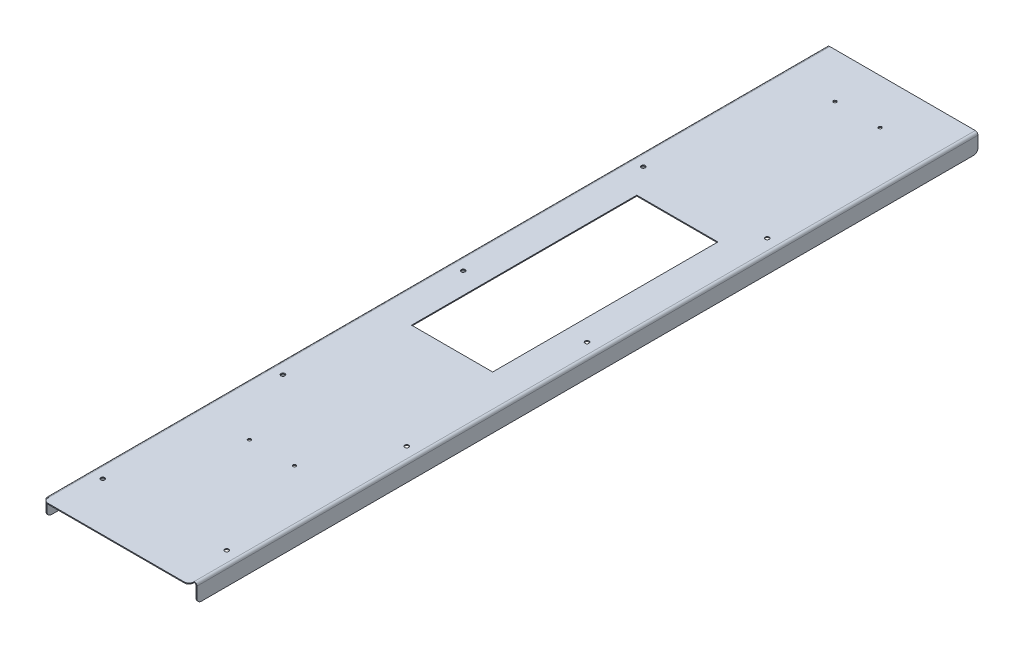
SolidWorks part; units mm, degrees
note: The reader was unsure of these and kept them because the rebuilt part matched: thickness of "Базовая кромка1", "Ребро-кромка1", "Листовой металл3", "Листовой металл4"; flange length of "Ребро-кромка1".
material "AISI 304"
ref_plane "Спереди" through (0, 0, 0) normal (0, 0, 1) x (1, 0, 0)
ref_plane "Сверху" through (0, 0, 0) normal (0, 1, 0) x (1, 0, 0)
ref_plane "Справа" through (0, 0, 0) normal (1, 0, 0) x (0, 0, -1)
sketch "Эскиз1" plane through (0, 0, 0) normal (0, 1, 0) x (1, 0, 0)
  line L0 (0, 373) -> (0, -127) construction
  line L1 (-161.5, 873) -> (161.5, 873)
  line L2 (-161.5, 873) -> (-161.5, -873)
  line L3 (-161.5, -873) -> (161.5, -873)
  line L4 (161.5, 873) -> (161.5, -873)
  line L5 (-161.5, 873) -> (161.5, -873) construction
  line L6 (-161.5, -873) -> (161.5, 873) construction
  line L9 (-90, 373) -> (90, 373)
  line L10 (-90, 373) -> (-90, -127)
  line L12 (-90, -127) -> (90, -127)
  line L13 (90, 373) -> (90, -127)
  line L14 (137.5, 873) -> (137.5, -873) construction
  line L15 (-137.5, 0) -> (137.5, 0) construction
  line L16 (-137.5, -873) -> (-137.5, 873) construction
  line L17 (-50, -527) -> (50, -527) construction
  line L18 (0, 0) -> (0, -527) construction
  line L19 (0, 0) -> (0, 773) construction
  line L20 (-50, 773) -> (50, 773) construction
  circle A0 centre (-137.5, -765) radius 4.5
  circle A1 centre (137.5, -765) radius 4.5
  circle A2 centre (-137.5, -365) radius 4.5
  circle A3 centre (137.5, -365) radius 4.5
  circle A4 centre (-137.5, 35) radius 4.5
  circle A5 centre (137.5, 35) radius 4.5
  circle A6 centre (-137.5, 435) radius 4.5
  circle A7 centre (137.5, 435) radius 4.5
  circle A18 centre (-50, -527) radius 3.5
  circle A19 centre (50, -527) radius 3.5
  circle A20 centre (-50, 773) radius 3.5
  circle A21 centre (50, 773) radius 3.5
  dimension "D6" = 275
  dimension "D7" = 9
  dimension "D8" = 108
  dimension "D11" = 7
  dimension "D1" = 746
  dimension "D2" = 323
  dimension "D3" = 180
  dimension "D4" = 500
  dimension "D5" = 500
  dimension "D10" = 400
  dimension "D12" = 100
  dimension "D13" = 400
  dimension "D14" = 400
  dimension "D9" = 4
base flange "Базовая кромка1" sketch "Эскиз1" thickness 2 reverse thickness direction no parameters "D1"=4
edge flange "Ребро-кромка1" sketch "Эскиз10" flange profiles "Эскиз10", "Эскиз11" flange angle 90 flange length 40 flange position bend outside bend radius 4 thickness 2 relief rectangular parameters "D6"=10, "D8"=1
sketch "Эскиз10" plane through (161.5, -2, 0) normal (1, 0, 0) x (0, 0, 1)
  line L2 (-873, 0) -> (-873, 38)
  line L3 (-873, 38) -> (861, 38)
  line L4 (861, 38) -> (861, 0)
  line L7 (873, 0) -> (-873, 0) construction
  line L8 (861, 0) -> (-873, 0)
  dimension "D1" = 12
sketch "Эскиз11" plane through (-161.5, -2, 0) normal (-1, 0, 0) x (0, 0, -1)
  line L0 (-873, 0) -> (-873, -2) construction
  line L2 (-861, 0) -> (-861, 38)
  line L3 (-861, 38) -> (873, 38)
  line L4 (873, 38) -> (873, 0)
  line L7 (873, 0) -> (-873, 0) construction
  line L8 (873, 0) -> (-861, 0)
  dimension "D1" = 12
bend "EdgeBend1" bend radius 4 bend angle 90 parameters "D5"=1
bend "EdgeBend2" bend radius 4 bend angle 90 parameters "D5"=2
fillet "Скругление1" radius 10 4 edges at (-166.5, -40, 861) (166.5, -40, 861) (166.5, -40, -873) (-166.5, -40, -873)
fillet "Скругление2" radius 10 2 edges at (161.5, -1, 873) (-161.5, -1, 873)
sketch "Сгиб-Линии1" plane through (0, 0, 0) normal (0, 1, 0) x (1, 0, 0)
sketch "Граничная рамка1" plane through (0, 0, 0) normal (0, 1, 0) x (1, 0, 0)
sheet metal parameters "Листовой металл3" thickness 2 parameters "D1"=4
flat pattern "Развертка3" [suppressed]
sketch "Сгиб-Линии2" plane through (0, 0, 0) normal (0, 1, 0) x (1, 0, 0)
sketch "Граничная рамка2" [suppressed] plane through (0, 0, 0) normal (0, 1, 0) x (1, 0, 0)
sheet metal parameters "Листовой металл4" thickness 2 parameters "D1"=4, "D7"=4
flat pattern "Развертка3" [suppressed]
sketch "Сгиб-Линии2" plane through (0, 0, 0) normal (0, 1, 0) x (1, 0, 0)
sketch "Граничная рамка2" [suppressed] plane through (0, 0, 0) normal (0, 1, 0) x (1, 0, 0)
bend of the flat pattern "Плоское состояние-<EdgeBend1>1"
bend of the flat pattern "Плоское состояние-<EdgeBend2>1"
